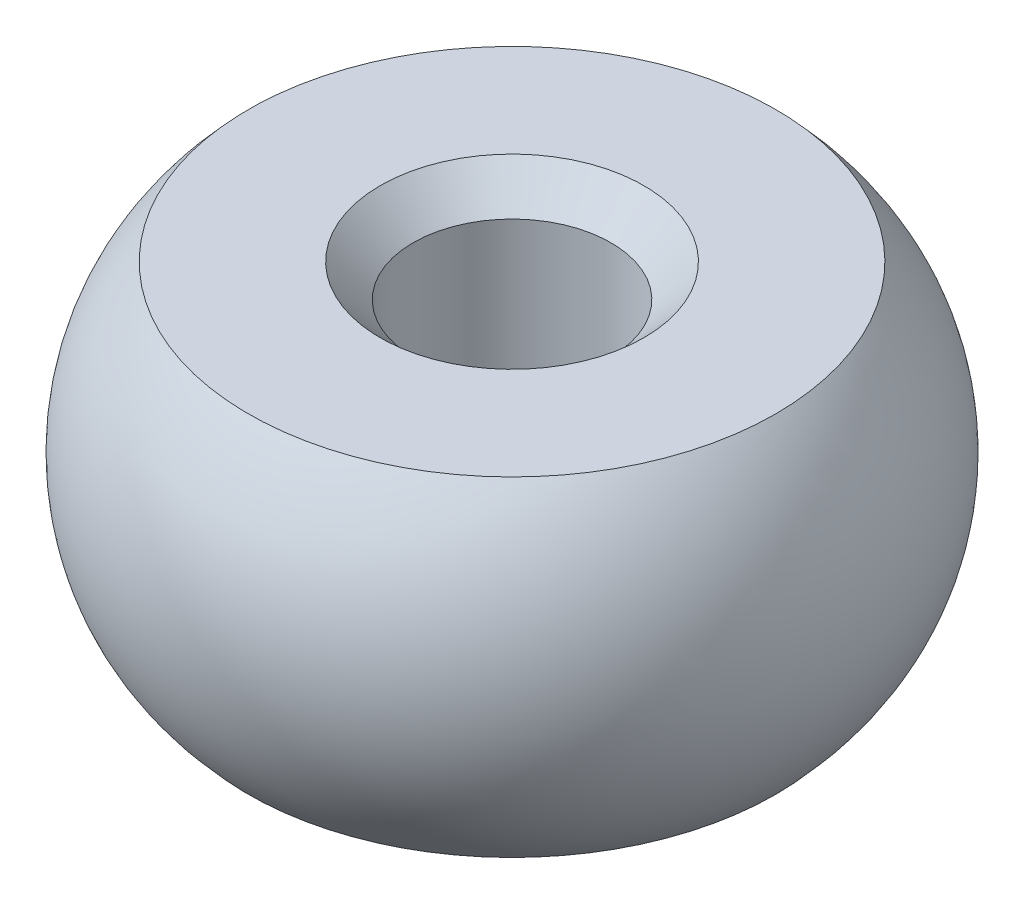
SolidWorks part; units mm, degrees
material "AISI Type A2 Tool Steel"
ref_plane "Front Plane" through (0, 0, 0) normal (0, 0, 1) x (1, 0, 0)
ref_plane "Top Plane" through (0, 0, 0) normal (0, 1, 0) x (1, 0, 0)
ref_plane "Right Plane" through (0, 0, 0) normal (1, 0, 0) x (0, 0, -1)
sketch "Sketch1" plane through (0, 0, 0) normal (0, 0, 1) x (1, 0, 0)
  line L0 (0, -90.7239) -> (0, 4445.4693) construction
  line L1 (1.5, 2.5) -> (1.5, -2.5)
  line L2 (1.5, 2.5) -> (4, 2.5)
  line L3 (1.5, -2.5) -> (4, -2.5)
  arc A1 (4, 2.5) -> (4, -2.5) centre (1.375, 0) cw
  point P5 (1.5, 0)
  point P11 (5, 0)
  dimension "D3" = 10
  dimension "D4" = 2.5
  dimension "D1" = 5
  dimension "D2" = 3
revolve "Revolve1" add sketch "Sketch1" angle 360 about L0
chamfer "Chamfer1" distance 0.5 angle 45 2 edges at (1.5, 2.5, 0) (1.5, -2.5, 0)
